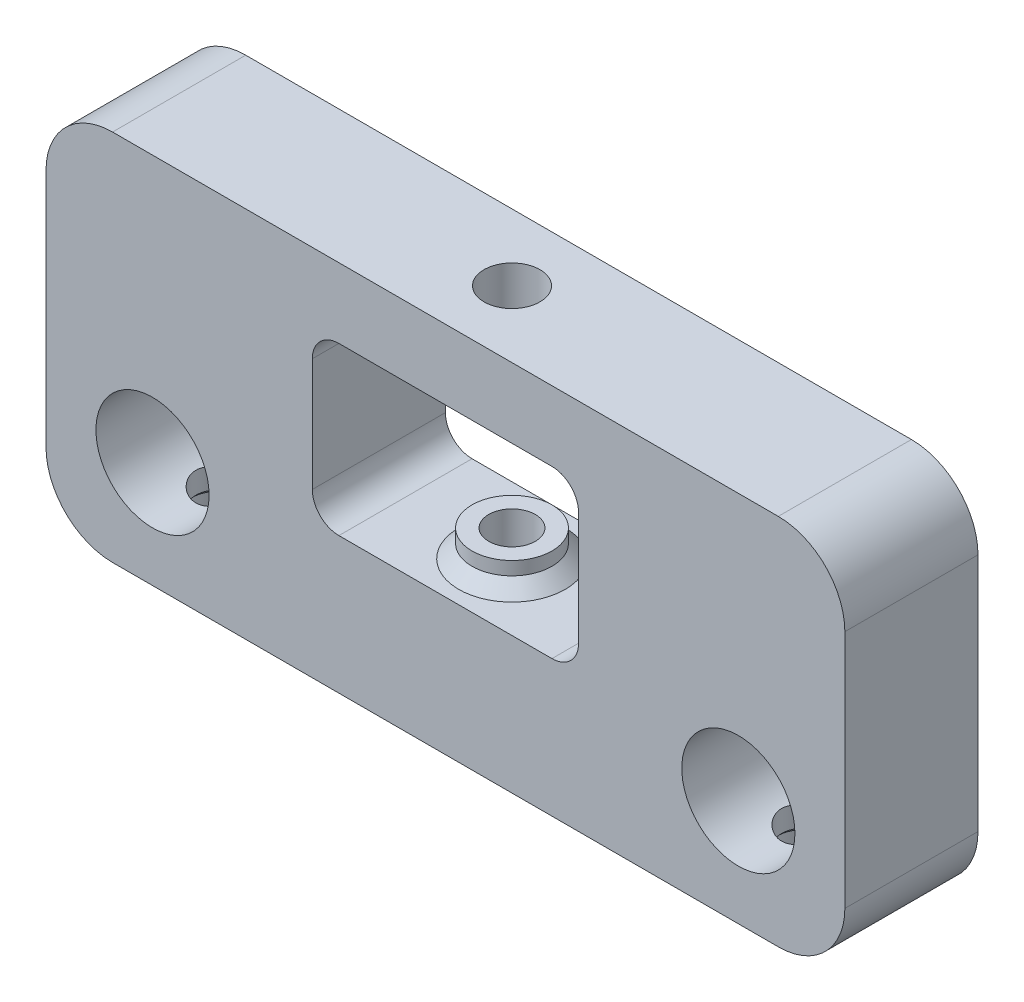
SolidWorks part; units mm, degrees
ref_plane "Front Plane" through (0, 0, 0) normal (0, 0, 1) x (1, 0, 0)
ref_plane "Top Plane" through (0, 0, 0) normal (0, 1, 0) x (1, 0, 0)
ref_plane "Right Plane" through (0, 0, 0) normal (1, 0, 0) x (0, 0, -1)
sketch "Sketch1" plane through (0, 0, 0) normal (0, 0, 1) x (1, 0, 0)
  line L0 (-30, 14) -> (30, -14) construction
  line L1 (-30, 14) -> (30, 14)
  line L2 (-30, 14) -> (-30, -14)
  line L3 (-30, -14) -> (30, -14)
  line L4 (30, 14) -> (30, -14)
  line L5 (0, 0) -> (0, 36.8289) construction
  circle A0 centre (-22, -6) radius 4.25
  circle A1 centre (22, -6) radius 4.25
  point P4 (0, 0)
  point P12 (26.25, -6)
  dimension "D3" = 8.5
  dimension "D1" = 60
  dimension "D2" = 28
  dimension "D4" = 44
  dimension "D5" = 8
  dimension "D6" = 8
  dimension "D7" = 3.75
extrude "Boss-Extrude1" add sketch "Sketch1" along normal mid plane 10
sketch "Sketch2" plane through (0, 0, -5) normal (0, 0, -1) x (-1, 0, 0)
  line L0 (10, -3.75) -> (-10, 8.75) construction
  line L1 (10, -3.75) -> (-10, -3.75)
  line L2 (10, -3.75) -> (10, 8.75)
  line L3 (10, 8.75) -> (-10, 8.75)
  line L4 (-10, -3.75) -> (-10, 8.75)
  line L5 (0, 2.5) -> (0, -22.2532) construction
  line L6 (-30, 14) -> (30, 14) construction
  dimension "D1" = 12.5
  dimension "D2" = 20
  dimension "D3" = 5.25
extrude "Cut-Extrude1" cut sketch "Sketch2" against normal through all
sketch "Sketch3" plane through (0, 14, 0) normal (0, 1, 0) x (1, 0, 0)
  circle A0 centre (0, 0) radius 1.75
  dimension "D1" = 3.5
extrude "Cut-Extrude2" cut sketch "Sketch3" against normal blind 30
sketch "Sketch4" plane through (0, -14, 0) normal (0, 1, 0) x (1, 0, 0)
  line L0 (0, 0) -> (0, 24.2319) construction
  circle A0 centre (-22, 0) radius 1.75
  circle A1 centre (22, 0) radius 1.75
  dimension "D1" = 3.5
  dimension "D2" = 44
extrude "Cut-Extrude3" cut sketch "Sketch4" along normal up to next
fillet "Fillet1" radius 5 4 edges at (30, 14, 0) (30, -14, 0) (-30, -14, 0) (-30, 14, 0)
fillet "Fillet2" radius 2 4 edges at (10, -3.75, 0) (10, 8.75, 0) (-10, -3.75, 0) (-10, 8.75, 0)
sketch "Sketch5" plane through (0, -14, 0) normal (0, -1, 0) x (1, 0, 0)
  circle A0 centre (0, 0) radius 3.25
  dimension "D1" = 6.5
extrude "Cut-Extrude4" cut sketch "Sketch5" against normal blind 4
sketch "Sketch6" plane through (0, -14, 0) normal (0, 1, 0) x (1, 0, 0)
  circle A0 centre (-22, 0) radius 2.1
  circle A1 centre (22, 0) radius 2.1
  dimension "D1" = 4.2
extrude "Cut-Extrude5" cut sketch "Sketch6" along normal blind 2
sketch "Sketch7" plane through (0, 8.75, 0) normal (0, -1, 0) x (1, 0, 0)
  circle A0 centre (0, 0) radius 3
  circle A1 centre (0, 0) radius 1.75 construction
  circle A2 centre (0, 0) radius 1.75
  dimension "D1" = 6
extrude "Boss-Extrude2" add sketch "Sketch7" along normal blind 2
sketch "Sketch8" plane through (0, -3.75, 0) normal (0, 1, 0) x (1, 0, 0)
  circle A0 centre (0, 0) radius 3
  circle A1 centre (0, 0) radius 1.75 construction
  circle A2 centre (0, 0) radius 1.75
  dimension "D1" = 6
extrude "Boss-Extrude3" add sketch "Sketch8" along normal blind 2
sketch "Sketch9" plane through (0, 14, 0) normal (0, 1, 0) x (1, 0, 0)
  circle A0 centre (0, 0) radius 2.1
  dimension "D1" = 4.2
extrude "Cut-Extrude6" cut sketch "Sketch9" against normal blind 3
chamfer "Chamfer1" distance 0.5 angle 45 3 edges at (22, -12, 1.75) (-22, -12, 1.75) (0, 11, 1.75)
chamfer "Chamfer2" distance 1 angle 45 2 edges at (-3, 8.75, 0) (3, -3.75, 0)
